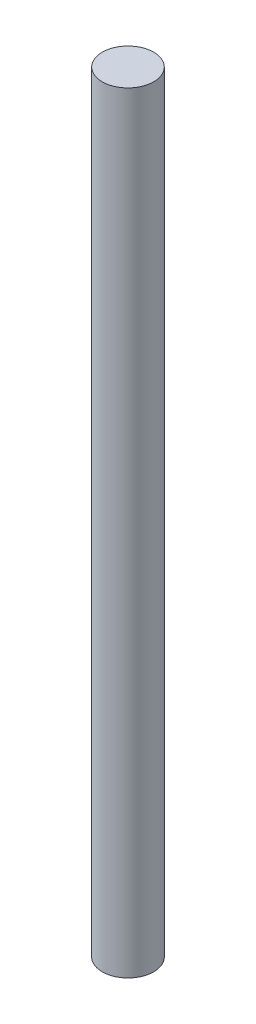
SolidWorks part; units mm, degrees
ref_plane "Front Plane" through (0, 0, 0) normal (0, 0, 1) x (1, 0, 0)
ref_plane "Top Plane" through (0, 0, 0) normal (0, 1, 0) x (1, 0, 0)
ref_plane "Right Plane" through (0, 0, 0) normal (1, 0, 0) x (0, 0, -1)
sketch "Sketch1" plane through (0, 0, 0) normal (0, 1, 0) x (1, 0, 0)
  circle A0 centre (0, 0) radius 12.7
  dimension "D1" = 25.4
extrude "Boss-Extrude1" add sketch "Sketch1" along normal blind 381
